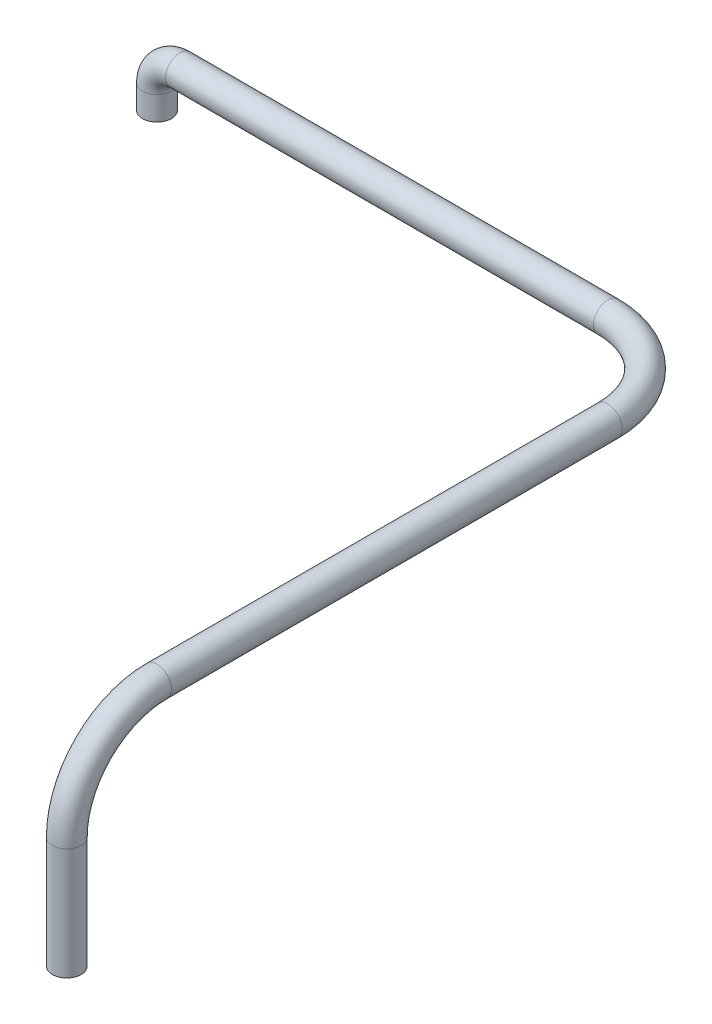
SolidWorks part; units mm, degrees
ref_plane "Front Plane" through (0, 0, 0) normal (0, 0, 1) x (1, 0, 0)
ref_plane "Top Plane" through (0, 0, 0) normal (0, 1, 0) x (1, 0, 0)
ref_plane "Right Plane" through (0, 0, 0) normal (1, 0, 0) x (0, 0, -1)
sketch "Sketch1" plane through (0, 0, 0) normal (0, 1, 0) x (1, 0, 0)
  circle A0 centre (0, 0) radius 4
  circle A1 centre (0, 0) radius 4
sketch3d "3DSketch1"
  line L0 (0, 0, 0) -> (0, 31, 0)
  line L1 (0, 56, -25) -> (0, 56, -150)
  line L2 (-25, 56, -175) -> (-143.63, 56, -175)
  line L3 (-150, 49.63, -175) -> (-150, 43, -175)
  arc A0 (0, 31, 0) -> (0, 56, -25) centre (0, 31, -25) cw
  arc A1 (0, 56, -150) -> (-25, 56, -175) centre (-25, 56, -150) cw
  arc A2 (-143.63, 56, -175) -> (-150, 49.63, -175) centre (-143.63, 49.63, -175) cw
  point P4 (-25, 31, -25)
  point P11 (-25, 81, -150)
  point P18 (-143.63, 49.63, -168.63)
sweep "Sweep1" add path "3DSketch1" circular profile diameter 8 parameters "D3"=8
sweep "Hollow_tube_OD_and_wall_PROVISIONAL" cut path "3DSketch1<2>" circular profile diameter 6 parameters "D3"=6
sketch3d "3DSketch1<2>" same geometry as "3DSketch1"
